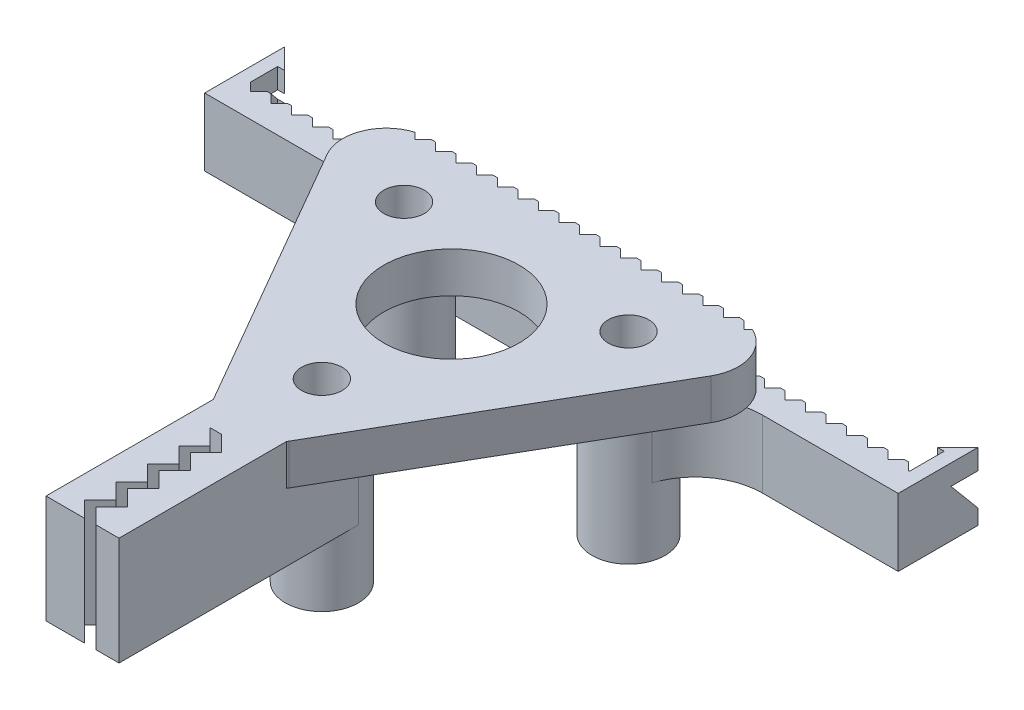
SolidWorks part; units mm, degrees
ref_plane "Front Plane" through (0, 0, 0) normal (0, 0, 1) x (1, 0, 0)
ref_plane "Top Plane" through (0, 0, 0) normal (0, 1, 0) x (1, 0, 0)
ref_plane "Right Plane" through (0, 0, 0) normal (1, 0, 0) x (0, 0, -1)
sketch "Sketch1" plane through (0, 0, 0) normal (0, 1, 0) x (1, 0, 0)
  line L0 (0, 0) -> (16.6, 0) construction
  line L1 (16.6, 0) -> (8.3, -14.376) construction
  line L2 (8.3, -14.376) -> (0, 0) construction
  line L3 (8.3, 0) -> (8.3, -14.376) construction
  line L4 (-3.1177, 5) -> (19.7177, 5)
  line L5 (22.489, 0.2) -> (11.0713, -19.576)
  line L6 (5.5287, -19.576) -> (-5.889, 0.2)
  line L7 (25.2603, 5) -> (8.3, -24.376) construction
  line L8 (8.3, -24.376) -> (-8.6603, 5) construction
  line L9 (-8.6603, 5) -> (25.2603, 5) construction
  circle A0 centre (0, 0) radius 1.5
  circle A1 centre (16.6, 0) radius 1.5
  circle A2 centre (8.3, -14.376) radius 1.5
  arc A3 (11.0713, -19.576) -> (5.5287, -19.576) centre (8.3, -17.976) cw
  arc A4 (22.489, 0.2) -> (19.7177, 5) centre (19.7177, 1.8) ccw
  arc A5 (-5.889, 0.2) -> (-3.1177, 5) centre (-3.1177, 1.8) cw
  dimension "D3" = 3
  dimension "D4" = 3
  dimension "D5" = 3
  dimension "D7" = 3.2
  dimension "D1" = 16.6
  dimension "D2" = 16.6
  dimension "D6" = 5
extrude "Caster Base" add sketch "Sketch1" along normal blind 3
sketch "Sketch2" plane through (0, 0, 0) normal (0, -1, 0) x (1, 0, 0)
  circle A0 centre (8.3, 14.376) radius 2.7
  circle A1 centre (0, 0) radius 2.7
  circle A2 centre (16.6, 0) radius 2.7
  circle A3 centre (8.3, 14.376) radius 1.6
  circle A4 centre (0, 0) radius 1.6
  circle A5 centre (16.6, 0) radius 1.6
  dimension "D1" = 5.4
  dimension "D2" = 5.4
  dimension "D3" = 5.4
extrude "Caster Standoffs" add sketch "Sketch2" along normal blind 10
sketch "Sketch7" plane through (0, 3, 0) normal (0, 1, 0) x (1, 0, 0)
  line L0 (0, 0) -> (16.6, 0) construction
  line L1 (8.3, 0) -> (8.3, -14.376) construction
  line L2 (0, 0) -> (8.3, -14.376) construction
  line L3 (16.6, 0) -> (4.15, -7.188) construction
  circle A0 centre (8.3, -4.792) radius 5
  dimension "D1" = 10
extrude "Cut-Extrude4" cut sketch "Sketch7" against normal up to next
sketch "Sketch9" plane through (0, 0, 0) normal (1, 0, 0) x (0, 0, -1)
  line L1 (2.6, 0) -> (5, 0)
  line L2 (2.6, 0) -> (2.6, -5)
  line L3 (2.6, -5) -> (5, -5)
  line L4 (5, 0) -> (5, -5)
  line L5 (0.2, 0) -> (5, 0) construction
  dimension "D1" = 5
  dimension "D2" = 0.1
extrude "Boss-Extrude3" add sketch "Sketch9" along normal blind 25 and the other way blind 25 from offset 8.6566
sketch "Sketch10" plane through (0, -5, 0) normal (0, -1, 0) x (1, 0, 0)
  line L0 (-16.3434, -5) -> (-15.7434, -4.4)
  line L1 (-15.7434, -4.4) -> (-15.1434, -5)
  line L2 (-16.3434, -5) -> (33.6566, -5) construction
  line L3 (-15.1434, -5) -> (-16.3434, -5)
  dimension "D1" = 0.6
extrude "Cut-Extrude5" cut sketch "Sketch10" against normal up to next
pattern_linear "LPattern1" count 33 spacing 1.52 along (1, 0, 0) of "Cut-Extrude5"
sketch "Sketch11" plane through (0, -5, 0) normal (0, -1, 0) x (1, 0, 0)
  line L0 (-16.3434, -2.6) -> (-17.3434, -2.6)
  line L1 (-17.3434, -2.6) -> (-17.3434, -8.5)
  line L2 (-17.3434, -8.5) -> (-15.8434, -7)
  line L3 (-15.8434, -7) -> (-16.3434, -7)
  line L4 (-16.3434, -7) -> (-16.3434, -5)
  line L5 (-15.1434, -5) -> (-14.8234, -5) construction
  line L6 (8.3, 14.376) -> (8.3, -10.0713) construction
  line L7 (32.9434, -2.6) -> (32.9434, -5)
  line L8 (32.9434, -7) -> (32.9434, -5)
  line L9 (32.4434, -7) -> (32.9434, -7)
  line L10 (33.9434, -8.5) -> (32.4434, -7)
  line L11 (33.9434, -2.6) -> (33.9434, -8.5)
  line L12 (32.9434, -2.6) -> (33.9434, -2.6)
  line L110 (32.2966, -5) -> (32.8966, -4.4)
  line L111 (32.8966, -4.4) -> (33.4966, -5)
  line L112 (33.4966, -5) -> (33.6566, -5)
  line L113 (33.6566, -5) -> (33.6566, -2.6)
  line L114 (33.6566, -2.6) -> (17.328, -2.6)
  line L115 (15.872, -2.6) -> (0.728, -2.6)
  line L116 (-0.728, -2.6) -> (-16.3434, -2.6)
  line L117 (-16.3434, -2.6) -> (-16.3434, -5)
  line L118 (-16.3434, -5) -> (-15.7434, -4.4)
  line L119 (-15.7434, -4.4) -> (-15.1434, -5)
  line L120 (-15.1434, -5) -> (-14.8234, -5)
  line L121 (-14.8234, -5) -> (-14.2234, -4.4)
  line L122 (-14.2234, -4.4) -> (-13.6234, -5)
  line L123 (-13.6234, -5) -> (-13.3034, -5)
  line L124 (-13.3034, -5) -> (-12.7034, -4.4)
  line L125 (-12.7034, -4.4) -> (-12.1034, -5)
  line L126 (-12.1034, -5) -> (-11.7834, -5)
  line L127 (-11.7834, -5) -> (-11.1834, -4.4)
  line L128 (-11.1834, -4.4) -> (-10.5834, -5)
  line L129 (-10.5834, -5) -> (-10.2634, -5)
  line L130 (-10.2634, -5) -> (-9.6634, -4.4)
  line L131 (-9.6634, -4.4) -> (-9.0634, -5)
  line L132 (-9.0634, -5) -> (-8.7434, -5)
  line L133 (-8.7434, -5) -> (-8.1434, -4.4)
  line L134 (-8.1434, -4.4) -> (-7.5434, -5)
  line L135 (-7.5434, -5) -> (-7.2234, -5)
  line L136 (-7.2234, -5) -> (-6.6234, -4.4)
  line L137 (-6.6234, -4.4) -> (-6.0234, -5)
  line L138 (-6.0234, -5) -> (-5.7034, -5)
  line L139 (-5.7034, -5) -> (-5.1034, -4.4)
  line L140 (-5.1034, -4.4) -> (-4.5034, -5)
  line L141 (-4.5034, -5) -> (-4.1834, -5)
  line L142 (-4.1834, -5) -> (-3.5834, -4.4)
  line L143 (-3.5834, -4.4) -> (-2.9834, -5)
  line L144 (-2.9834, -5) -> (-2.6634, -5)
  line L145 (-2.6634, -5) -> (-2.0634, -4.4)
  line L146 (-2.0634, -4.4) -> (-1.4634, -5)
  line L147 (-1.4634, -5) -> (-1.1434, -5)
  line L148 (-1.1434, -5) -> (-0.5434, -4.4)
  line L149 (-0.5434, -4.4) -> (0.0566, -5)
  line L150 (0.0566, -5) -> (0.3766, -5)
  line L151 (0.3766, -5) -> (0.9766, -4.4)
  line L152 (0.9766, -4.4) -> (1.5766, -5)
  line L153 (1.5766, -5) -> (1.8966, -5)
  line L154 (1.8966, -5) -> (2.4966, -4.4)
  line L155 (2.4966, -4.4) -> (3.0966, -5)
  line L156 (3.0966, -5) -> (3.4166, -5)
  line L157 (3.4166, -5) -> (4.0166, -4.4)
  line L158 (4.0166, -4.4) -> (4.6166, -5)
  line L159 (4.6166, -5) -> (4.9366, -5)
  line L160 (4.9366, -5) -> (5.5366, -4.4)
  line L161 (5.5366, -4.4) -> (6.1366, -5)
  line L162 (6.1366, -5) -> (6.4566, -5)
  line L163 (6.4566, -5) -> (7.0566, -4.4)
  line L164 (7.0566, -4.4) -> (7.6566, -5)
  line L165 (7.6566, -5) -> (7.9766, -5)
  line L166 (7.9766, -5) -> (8.5766, -4.4)
  line L167 (8.5766, -4.4) -> (9.1766, -5)
  line L168 (9.1766, -5) -> (9.4966, -5)
  line L169 (9.4966, -5) -> (10.0966, -4.4)
  line L170 (10.0966, -4.4) -> (10.6966, -5)
  line L171 (10.6966, -5) -> (11.0166, -5)
  line L172 (11.0166, -5) -> (11.6166, -4.4)
  line L173 (11.6166, -4.4) -> (12.2166, -5)
  line L174 (12.2166, -5) -> (12.5366, -5)
  line L175 (12.5366, -5) -> (13.1366, -4.4)
  line L176 (13.1366, -4.4) -> (13.7366, -5)
  line L177 (13.7366, -5) -> (14.0566, -5)
  line L178 (14.0566, -5) -> (14.6566, -4.4)
  line L179 (14.6566, -4.4) -> (15.2566, -5)
  line L180 (15.2566, -5) -> (15.5766, -5)
  line L181 (15.5766, -5) -> (16.1766, -4.4)
  line L182 (16.1766, -4.4) -> (16.7766, -5)
  line L183 (16.7766, -5) -> (17.0966, -5)
  line L184 (17.0966, -5) -> (17.6966, -4.4)
  line L185 (17.6966, -4.4) -> (18.2966, -5)
  line L186 (18.2966, -5) -> (18.6166, -5)
  line L187 (18.6166, -5) -> (19.2166, -4.4)
  line L188 (19.2166, -4.4) -> (19.8166, -5)
  line L189 (19.8166, -5) -> (20.1366, -5)
  line L190 (20.1366, -5) -> (20.7366, -4.4)
  line L191 (20.7366, -4.4) -> (21.3366, -5)
  line L192 (21.3366, -5) -> (21.6566, -5)
  line L193 (21.6566, -5) -> (22.2566, -4.4)
  line L194 (22.2566, -4.4) -> (22.8566, -5)
  line L195 (22.8566, -5) -> (23.1766, -5)
  line L196 (23.1766, -5) -> (23.7766, -4.4)
  line L197 (23.7766, -4.4) -> (24.3766, -5)
  line L198 (24.3766, -5) -> (24.6966, -5)
  line L199 (24.6966, -5) -> (25.2966, -4.4)
  line L200 (25.2966, -4.4) -> (25.8966, -5)
  line L201 (25.8966, -5) -> (26.2166, -5)
  line L202 (26.2166, -5) -> (26.8166, -4.4)
  line L203 (26.8166, -4.4) -> (27.4166, -5)
  line L204 (27.4166, -5) -> (27.7366, -5)
  line L205 (27.7366, -5) -> (28.3366, -4.4)
  line L206 (28.3366, -4.4) -> (28.9366, -5)
  line L207 (28.9366, -5) -> (29.2566, -5)
  line L208 (29.2566, -5) -> (29.8566, -4.4)
  line L209 (29.8566, -4.4) -> (30.4566, -5)
  line L210 (30.4566, -5) -> (30.7766, -5)
  line L211 (30.7766, -5) -> (31.3766, -4.4)
  line L212 (31.3766, -4.4) -> (31.9766, -5)
  line L213 (31.9766, -5) -> (32.2966, -5)
  line L221 (-16.3434, -2.6) -> (-16.3434, -5)
  arc A2 (15.872, -2.6) -> (17.328, -2.6) centre (16.6, 0) ccw
  arc A3 (-0.728, -2.6) -> (0.728, -2.6) centre (0, 0) ccw
  dimension "D1" = 1
  dimension "D2" = 0.5
  dimension "D3" = 45
  dimension "D4" = 2
  dimension "D5" = 0
extrude "Boss-Extrude4" add sketch "Sketch11" against normal up to surface (5 mm away) up to face at (-10.0445, 0, -4.6624)
ref_plane "Plane1" through (0, 0, 17.076) normal (0, 0, 1) x (1, 0, 0)
sketch "Sketch12" plane through (0, 0, 17.076) normal (0, 0, 1) x (1, 0, 0)
  line L0 (5.6, 0) -> (5.6, -10) construction
  line L1 (5.6, 3) -> (11, 3)
  line L2 (5.6, 3) -> (5.6, -5)
  line L3 (5.6, -5) -> (11, -5)
  line L4 (11, 3) -> (11, -5)
  line L5 (11, -10) -> (11, 0) construction
  line L7 (11.0713, 3) -> (5.5287, 3) construction
  dimension "D1" = 8
extrude "Boss-Extrude5" add sketch "Sketch12" along normal blind 15 and the other way blind 2.7
fillet "Fillet1" radius 5 1 edges at (17.328, -2.5, -2.6)
sketch "Sketch13" plane through (0, 3, 0) normal (0, 1, 0) x (1, 0, 0)
  line L0 (9.8, -14.376) -> (6.8, -14.376) construction
  line L1 (8.4602, -20.4738) -> (7.3, -21.6341)
  line L2 (7.3, -21.6341) -> (8.4602, -22.7943)
  line L3 (8.4602, -22.7943) -> (7.3, -23.9545)
  line L4 (7.3, -23.9545) -> (8.4602, -25.1147)
  line L5 (8.4602, -25.1147) -> (7.3, -26.2749)
  line L6 (7.3, -26.2749) -> (8.4602, -27.4351)
  line L7 (8.4602, -27.4351) -> (7.3, -28.5954)
  line L8 (7.3, -28.5954) -> (8.4602, -29.7556)
  line L9 (8.4602, -29.7556) -> (7.3, -30.9158)
  line L10 (7.3, -30.9158) -> (8.4602, -32.076)
  line L11 (11, -32.076) -> (5.6, -32.076) construction
  line L12 (8.8845, -20.8981) -> (8.1485, -21.6341)
  line L13 (8.1485, -21.6341) -> (9.3087, -22.7943)
  line L14 (9.3087, -22.7943) -> (8.1485, -23.9545)
  line L15 (8.1485, -23.9545) -> (9.3087, -25.1147)
  line L16 (9.3087, -25.1147) -> (8.1485, -26.2749)
  line L17 (8.1485, -26.2749) -> (9.3087, -27.4351)
  line L18 (9.3087, -27.4351) -> (8.1485, -28.5954)
  line L19 (8.1485, -28.5954) -> (9.3087, -29.7556)
  line L20 (9.3087, -29.7556) -> (8.1485, -30.9158)
  line L21 (8.1485, -30.9158) -> (8.8845, -31.6518)
  line L22 (8.8845, -31.6518) -> (9.3087, -32.076)
  line L23 (7.3, -21.6341) -> (8.1485, -21.6341)
  line L24 (8.4602, -32.076) -> (9.3087, -32.076)
  line L25 (8.8845, -32.076) -> (5.6, -32.076) construction
  line L26 (5.6, -19.6936) -> (5.6, -32.076) construction
  circle A0 centre (8.3, -14.376) radius 1.5
  dimension "D2" = 1.7
  dimension "D1" = 0.6
extrude "Cut-Extrude6" cut sketch "Sketch13" against normal through all contours L10 L24 L22 L21 L20 L19 L18 L17 L16 L15 L14 L13 L23 L2 L3 L4 L5 L6 L7 L8 L9 | A0
sketch "Sketch14" plane through (-17.3434, 0, 0) normal (-1, 0, 0) x (0, 0, 1)
  line L0 (-8.5, -1.5) -> (-6.5, -1.5)
  line L1 (-8.5, 0) -> (-8.5, -5) construction
  line L2 (-6.5, -1.5) -> (-8.5, -3.8835)
  line L3 (-2.6, 0) -> (-8.5, 0) construction
  line L4 (-8.5, -1.5) -> (-8.5, -3.8835)
  dimension "D1" = 50
  dimension "D2" = 2
  dimension "D3" = 1.5
extrude "Cut-Extrude7" cut sketch "Sketch14" against normal through all
equation "\"D2@Sketch1\"=\"D1@Sketch1\""
equation "\"D4@Sketch1\"=\"D3@Sketch1\""
equation "\"D5@Sketch1\"=\"D3@Sketch1\""
equation "\"D2@Sketch2\"=\"D1@Sketch2\""
equation "\"D3@Sketch2\"=\"D1@Sketch2\""
